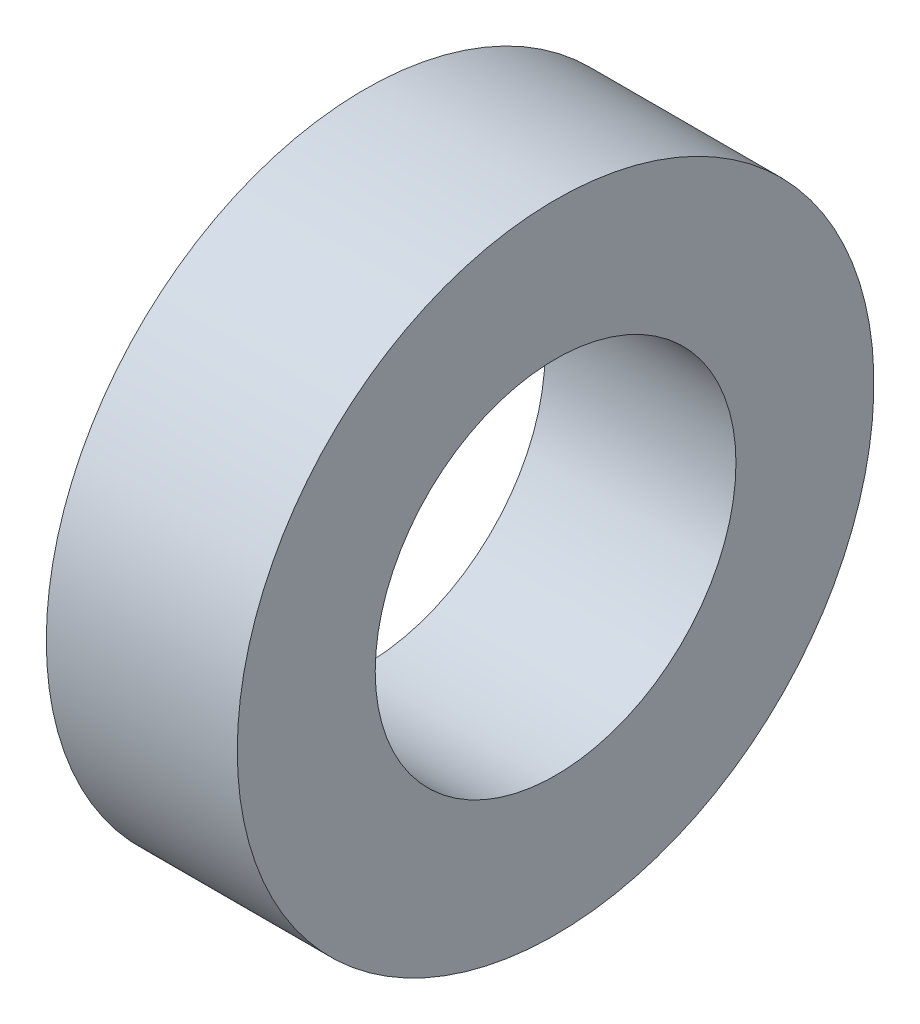
SolidWorks part; units mm, degrees
material "AISI 316 (1.4401)"
ref_plane "Płaszczyzna przednia" through (0, 0, 0) normal (0, 0, 1) x (1, 0, 0)
ref_plane "Płaszczyzna górna" through (0, 0, 0) normal (0, 1, 0) x (1, 0, 0)
ref_plane "Płaszczyzna prawa" through (0, 0, 0) normal (1, 0, 0) x (0, 0, -1)
sketch "Szkic1" plane through (0, 0, 0) normal (0, 0, 1) x (1, 0, 0)
  line L0 (0, 0) -> (9, 0) construction
  line L2 (0, 8.5) -> (9, 8.5)
  line L3 (0, 8.5) -> (0, 15)
  line L4 (0, 15) -> (9, 15)
  line L5 (9, 8.5) -> (9, 15)
  dimension "D1" = 17
  dimension "D2" = 30
  dimension "D3" = 9
revolve "Obrót1" add sketch "Szkic1" angle 360 about L0
